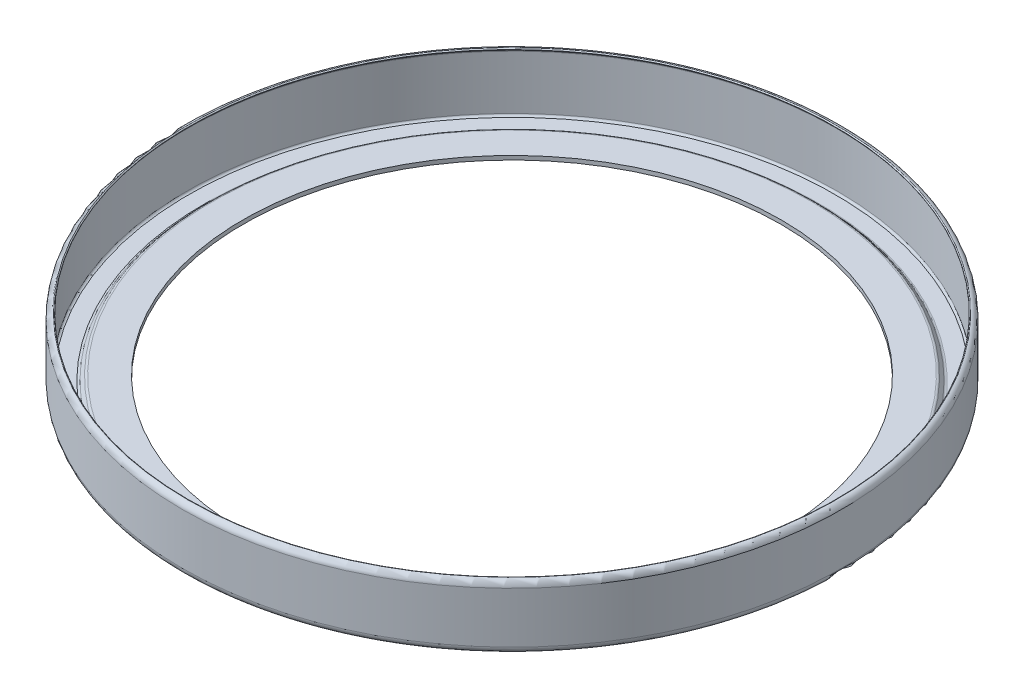
SolidWorks part; units mm, degrees
ref_plane "Plano frontal" through (0, 0, 0) normal (0, 0, 1) x (1, 0, 0)
ref_plane "Plano superior" through (0, 0, 0) normal (0, 1, 0) x (1, 0, 0)
ref_plane "Plano direito" through (0, 0, 0) normal (1, 0, 0) x (0, 0, -1)
sketch "Esboço1" plane through (0, 0, 0) normal (0, 0, 1) x (1, 0, 0)
  line L0 (0, -52.0025) -> (0, 59.6534) construction
  line L1 (81, 7.5756) -> (81, 8.0756)
  line L2 (81, 8.0756) -> (82.55, 8.0756)
  line L3 (82.55, 8.0756) -> (82.55, -7.9244)
  line L4 (82.55, -7.9244) -> (76.75, -7.9244)
  line L5 (76.75, -7.9244) -> (75.5, -6.5244)
  line L6 (75.5, -6.5244) -> (67.4, -6.5244)
  line L7 (67.4, -6.5244) -> (67.4, -5.5244)
  line L8 (67.4, -5.5244) -> (75.5, -5.5244)
  line L9 (75.5, -5.5244) -> (76.75, -6.9244)
  line L10 (76.75, -6.9244) -> (81.55, -6.9244)
  line L11 (81.55, -6.9244) -> (81.55, 7.5756)
  line L12 (81.55, 7.5756) -> (81, 7.5756)
  dimension "D1" = 67.4
  dimension "D2" = 75.5
  dimension "D3" = 75.5
  dimension "D4" = 76.75
  dimension "D5" = 76.75
  dimension "D6" = 82.55
  dimension "D7" = 1
  dimension "D8" = 81
  dimension "D9" = 0.5
  dimension "D10" = 1
  dimension "D11" = 2.4
  dimension "D12" = 16
revolve "Revolução1" add sketch "Esboço1" angle 360 about L0
fillet "Filete2" radius 0.25 2 edges at (0, 7.5756, -81) (0, 8.0756, -81)
fillet "Filete3" radius 1.5 1 edges at (0, 8.0756, -82.55)
fillet "Filete4" radius 0.5 1 edges at (0, 7.5756, -81.55)
fillet "Filete5" radius 1.75 1 edges at (0, -7.9244, -82.55)
fillet "Filete6" radius 0.5 1 edges at (0, -6.9244, -81.55)
fillet "Filete7" radius 0.75 4 edges at (0, -7.9244, -76.75) (0, -6.9244, -76.75) (0, -6.5244, -75.5) (0, -5.5244, -75.5)
